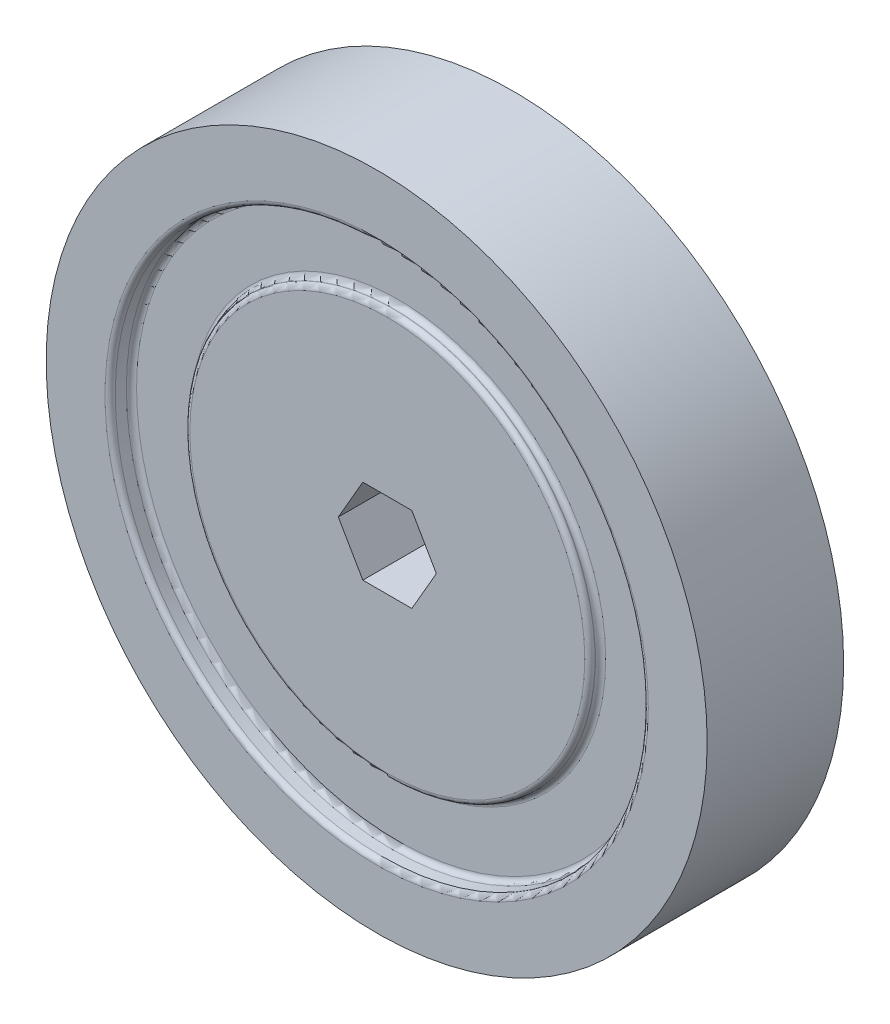
SolidWorks part; units mm, degrees
ref_plane "Front Plane" through (0, 0, 0) normal (0, 0, 1) x (1, 0, 0)
ref_plane "Top Plane" through (0, 0, 0) normal (0, 1, 0) x (1, 0, 0)
ref_plane "Right Plane" through (0, 0, 0) normal (1, 0, 0) x (0, 0, -1)
sketch "Sketch1" plane through (0, 0, 0) normal (0, 0, 1) x (1, 0, 0)
  circle A0 centre (0, 0) radius 49.2125
  dimension "D1" = 98.425
extrude "Boss-Extrude1" add sketch "Sketch1" along normal blind 10.16 and the other way blind 10.16
sketch "Sketch2" plane through (0, 0, 10.16) normal (0, 0, 1) x (1, 0, 0)
  line L1 (3.6489, 6.32) -> (-3.6489, 6.32)
  line L2 (-3.6489, 6.32) -> (-7.2977, 0)
  line L3 (-7.2977, 0) -> (-3.6489, -6.32)
  line L4 (-3.6489, -6.32) -> (3.6489, -6.32)
  line L5 (3.6489, -6.32) -> (7.2977, 0)
  line L6 (7.2977, 0) -> (3.6489, 6.32)
  circle A0 centre (0, 0) radius 6.32 construction
  dimension "D1" = 12.64
extrude "Cut-Extrude1" cut sketch "Sketch2" against normal through all
sketch "Sketch3" plane through (0, 0, 0) normal (1, 0, 0) x (0, 0, -1)
  line L0 (8.5725, 30.1625) -> (6.985, 30.1625)
  line L1 (10.16, -49.2125) -> (10.16, 49.2125) construction
  line L2 (6.985, 30.1625) -> (6.985, 39.6875)
  line L3 (6.985, 39.6875) -> (10.16, 39.6875)
  line L4 (10.16, 39.6875) -> (10.16, 0)
  line L5 (22.753, 0) -> (-27.7028, 0) construction
  line L6 (10.16, 49.2125) -> (-10.16, 49.2125) construction
  line L7 (10.16, 0) -> (8.5725, 0)
  line L8 (8.5725, 0) -> (8.5725, 30.1625)
  dimension "D1" = 9.525
  dimension "D2" = 9.525
  dimension "D3" = 1.5875
  dimension "D4" = 3.175
revolve "Cut-Revolve1" cut sketch "Sketch3" angle 360 about L5
fillet "Fillet1" radius 0.762 3 edges at (-30.1625, 0, -6.985) (-39.6875, 0, -10.16) (-30.1625, 0, -8.5725)
mirror "Mirror1" about plane through (0, 0, 0) normal (0, 0, 1) of "Cut-Revolve1"
fillet "Fillet2" radius 0.762 4 edges at (-39.6875, 0, 10.16) (-39.6875, 0, 6.985) (-30.1625, 0, 6.985) (-30.1625, 0, 8.5725)
